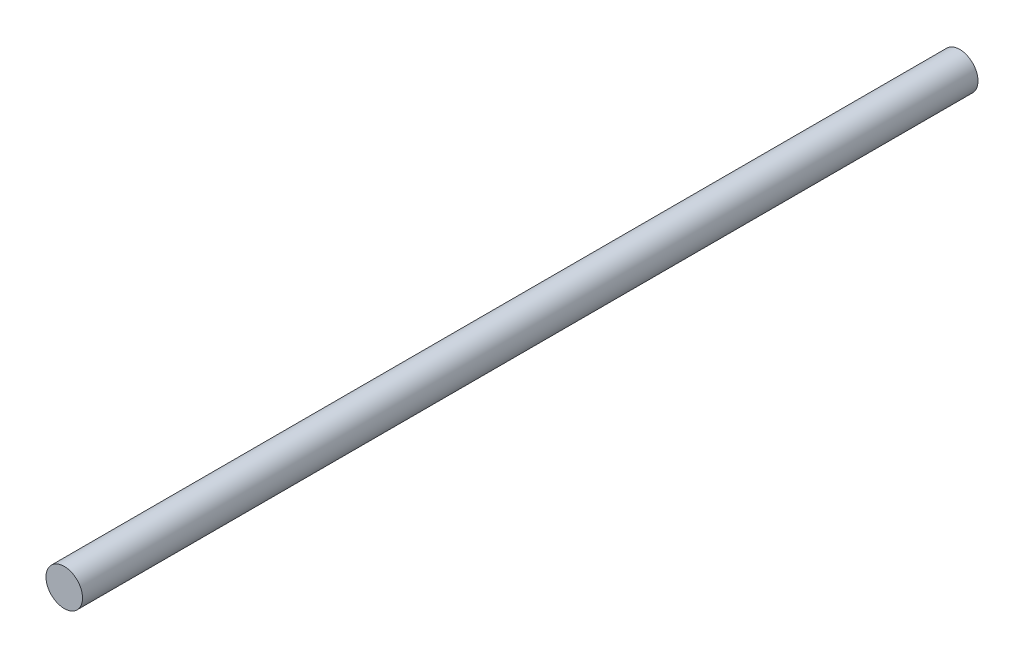
SolidWorks part; units mm, degrees
ref_plane "Front Plane" through (0, 0, 0) normal (0, 0, 1) x (1, 0, 0)
ref_plane "Top Plane" through (0, 0, 0) normal (0, 1, 0) x (1, 0, 0)
ref_plane "Right Plane" through (0, 0, 0) normal (1, 0, 0) x (0, 0, -1)
sketch "Sketch1" plane through (0, 0, 0) normal (0, 0, 1) x (1, 0, 0)
  circle A0 centre (0, 0) radius 6.35
  dimension "D1" = 12.7
extrude "Boss-Extrude1" add sketch "Sketch1" along normal blind 311.15
